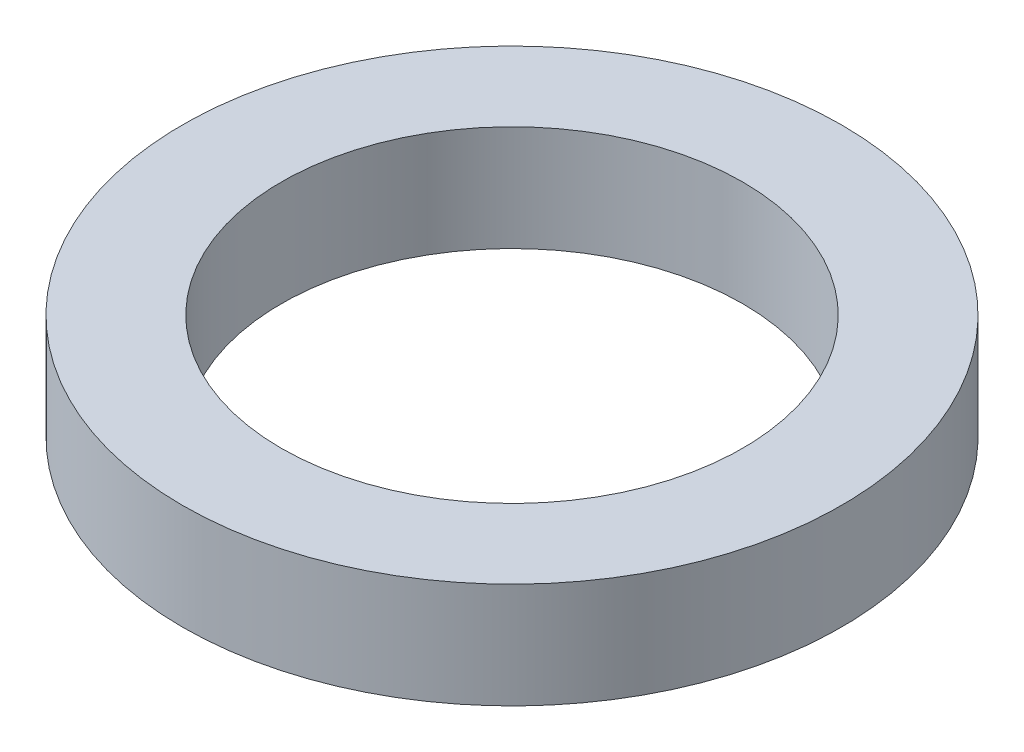
SolidWorks part; units mm, degrees
ref_plane "Front Plane" through (0, 0, 0) normal (0, 0, 1) x (1, 0, 0)
ref_plane "Top Plane" through (0, 0, 0) normal (0, 1, 0) x (1, 0, 0)
ref_plane "Right Plane" through (0, 0, 0) normal (1, 0, 0) x (0, 0, -1)
sketch "Sketch1" plane through (0, 0, 0) normal (0, 1, 0) x (1, 0, 0)
  circle A0 centre (0, 0) radius 25
  dimension "FLANGE_OD" = 50
extrude "Boss-Extrude1" add sketch "Sketch1" along normal blind 8
sketch "Sketch2" plane through (0, 0, 0) normal (0, 1, 0) x (1, 0, 0)
  circle A0 centre (0, 0) radius 17.5
  dimension "BORE_D" = 35
extrude "Cut-Extrude1" cut sketch "Sketch2" along normal through all
sketch "Sketch3" plane through (0, 8, 0) normal (0, 1, 0) x (1, 0, 0)
  circle A0 centre (0, 0) radius 10.835 construction
  circle A1 centre (-10.835, 0) radius 1.5
  dimension "BOLT_D" = 3
  dimension "BOLT_PCD" = 21.6701
extrude "Cut-Extrude2" cut sketch "Sketch3" against normal blind 7.2242 rebuild error yes
pattern_circular "CirPattern1" count 5 over 360 rebuild error yes
